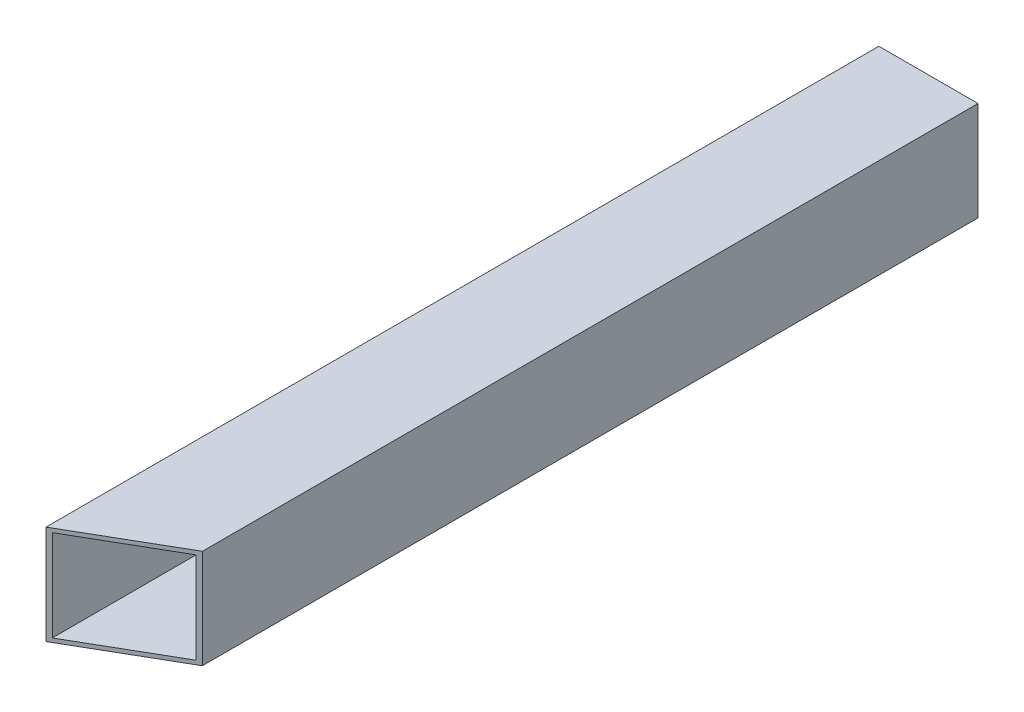
SolidWorks part; units mm, degrees
ref_plane "Front Plane" through (0, 0, 0) normal (0, 0, 1) x (1, 0, 0)
ref_plane "Top Plane" through (0, 0, 0) normal (0, 1, 0) x (1, 0, 0)
ref_plane "Right Plane" through (0, 0, 0) normal (1, 0, 0) x (0, 0, -1)
sketch "Sketch2" plane through (0, 0, 0) normal (0, 0, 1) x (1, 0, 0)
  line L1 (12.5, -12.5) -> (-12.5, -12.5)
  line L2 (12.5, -12.5) -> (12.5, 12.5)
  line L3 (12.5, 12.5) -> (-12.5, 12.5)
  line L4 (-12.5, -12.5) -> (-12.5, 12.5)
  line L5 (12.5, -12.5) -> (-12.5, 12.5) construction
  line L6 (12.5, 12.5) -> (-12.5, -12.5) construction
  line L7 (11.5, -11.5) -> (-11.5, -11.5)
  line L8 (11.5, -11.5) -> (11.5, 11.5)
  line L9 (11.5, 11.5) -> (-11.5, 11.5)
  line L10 (-11.5, -11.5) -> (-11.5, 11.5)
  line L11 (11.5, -11.5) -> (-11.5, 11.5) construction
  line L12 (11.5, 11.5) -> (-11.5, -11.5) construction
  point P0 (0, 0)
  point P6 (0, 0)
  dimension "D1" = 25
  dimension "D2" = 1
extrude "Boss-Extrude1" add sketch "Sketch2" along normal blind 210
sketch "Sketch3" plane through (0, 12.5, 0) normal (0, 1, 0) x (1, 0, 0)
  line L4 (12.5, -210) -> (12.5, -195.5662)
  line L5 (12.5, -210) -> (12.5, 0) construction
  line L6 (12.5, -195.5662) -> (-12.5, -210)
  line L7 (12.5, -210) -> (-12.5, -210) construction
  line L8 (-12.5, -210) -> (-12.5, 0) construction
  line L9 (-12.5, -210) -> (12.5, -210)
  dimension "D1" = 30
extrude "Cut-Extrude1" cut sketch "Sketch3" against normal blind 210
